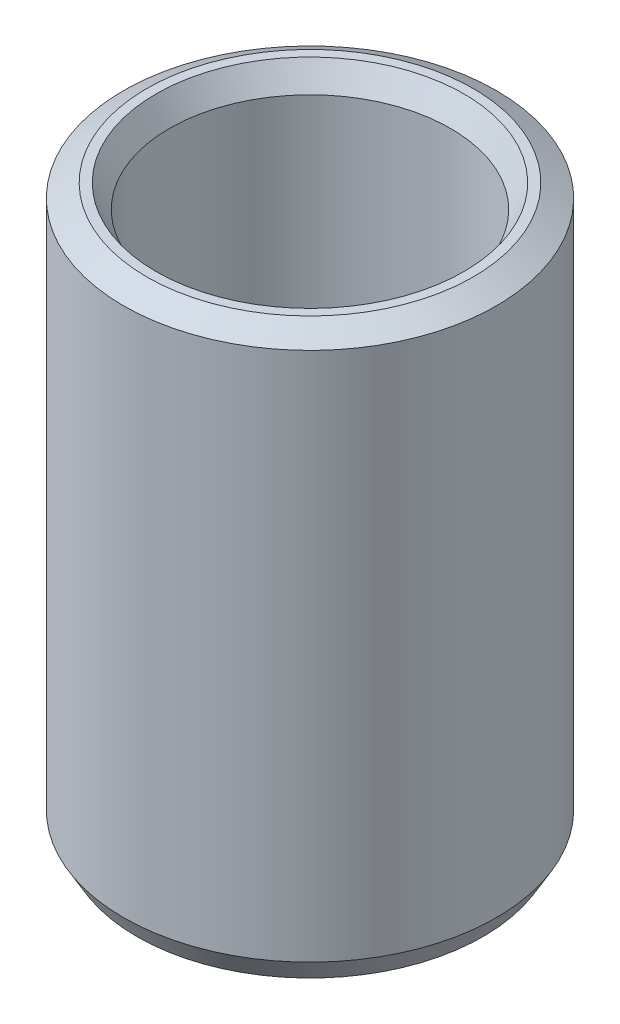
SolidWorks part; units mm, degrees
ref_plane "Front Plane" through (0, 0, 0) normal (0, 0, 1) x (1, 0, 0)
ref_plane "Top Plane" through (0, 0, 0) normal (0, 1, 0) x (1, 0, 0)
ref_plane "Right Plane" through (0, 0, 0) normal (1, 0, 0) x (0, 0, -1)
sketch "Sketch1" plane through (0, 0, 0) normal (0, 1, 0) x (1, 0, 0)
  circle A0 centre (0, 0) radius 27.5
  dimension "SLEEVE_OD" = 55
extrude "Boss-Extrude1" add sketch "Sketch1" along normal blind 83.5476
sketch "Sketch2" plane through (0, 0, 0) normal (0, 1, 0) x (1, 0, 0)
  circle A0 centre (0, 0) radius 20.7308
  dimension "BORE_D" = 41.4616
extrude "Cut-Extrude1" cut sketch "Sketch2" along normal through all
chamfer "Chamfer1" distance 1.976 angle 60 4 edges at (0, 83.5476, 20.7308) (0, 0, 20.7308) (0, 0, 27.5) (0, 83.5476, 27.5) first distance on face at (0, 83.5476, 20.7308) first distance on face at (0, 0, 20.7308) first distance on face at (0, 83.5476, 27.5)
